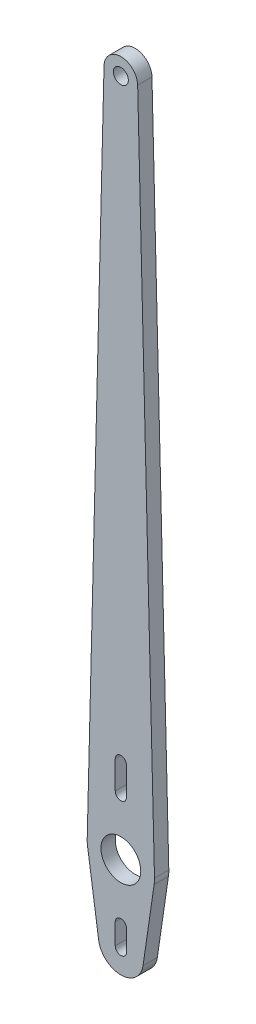
SolidWorks part; units mm, degrees
ref_plane "Front Plane" through (0, 0, 0) normal (0, 0, 1) x (1, 0, 0)
ref_plane "Top Plane" through (0, 0, 0) normal (0, 1, 0) x (1, 0, 0)
ref_plane "Right Plane" through (0, 0, 0) normal (1, 0, 0) x (0, 0, -1)
sketch "Model" plane through (0, 0, 0) normal (0, 0, 1) x (1, 0, 0)
  line L0 (-1, 18.4215) -> (-1, -3.4062) construction
  line L1 (1, 18.4215) -> (1, 5.9161) construction
  line L2 (-2.9991, 121.0744) -> (-5.9982, 0.1488)
  line L3 (-3.9578, -14.3797) -> (-5.9367, -0.8696)
  line L4 (0, 0) -> (0, 32.3338) construction
  line L5 (3.9578, -14.3797) -> (5.9367, -0.8696)
  line L6 (2.9991, 121.0744) -> (5.9982, 0.1488)
  line L7 (-7.5978, 10.1) -> (4.5933, 10.1) construction
  line L8 (-1.9126, -10.1) -> (1, -10.1) construction
  line L9 (-3.5953, 15.1) -> (3.0222, 15.1) construction
  line L10 (-2.3019, -13.8) -> (3.0222, -13.8) construction
  line L13 (-1, -10.1) -> (-1, -13.8)
  line L14 (1, -10.1) -> (1, -13.8)
  line L15 (-1, 15.1) -> (-1, 10.1)
  line L16 (1, 15.1) -> (1, 10.1)
  line L17 (1, 3.4062) -> (1, -5.9161) construction
  line L18 (1, -10.1) -> (1, -18.7667) construction
  line L19 (-1, -5.9161) -> (-1, -18.7667) construction
  circle A0 centre (0, 0) radius 3.55
  arc A1 (-5.9982, 0.1488) -> (-5.9367, -0.8696) centre (0, 0) ccw
  arc A2 (1, 15.1) -> (-1, 15.1) centre (0, 15.1) ccw
  arc A3 (-1, 10.1) -> (1, 10.1) centre (0, 10.1) ccw
  arc A4 (1, -10.1) -> (-1, -10.1) centre (0, -10.1) ccw
  arc A5 (-1, -13.8) -> (1, -13.8) centre (0, -13.8) ccw
  circle A6 centre (0, 121) radius 1.333
  arc A7 (2.9991, 121.0744) -> (-2.9991, 121.0744) centre (0, 121) ccw
  arc A8 (-3.9578, -14.3797) -> (3.9578, -14.3797) centre (0, -13.8) ccw
  arc A9 (5.9367, -0.8696) -> (5.9982, 0.1488) centre (0, 0) ccw
  point P44 (4, -4.4721)
  point P47 (-4, -4.4721)
  dimension "D1" = 7.1
  dimension "D2" = 12
  dimension "D15" = 2.666
  dimension "D5" = 3
  dimension "D3" = 1
  dimension "D4" = 1
  dimension "D9" = 10.1
  dimension "D10" = 10.1
  dimension "D11" = 3.7
  dimension "D12" = 5
  dimension "D16" = 121
extrude "Boss-Extrude1" add sketch "Model" along normal blind 2.55
